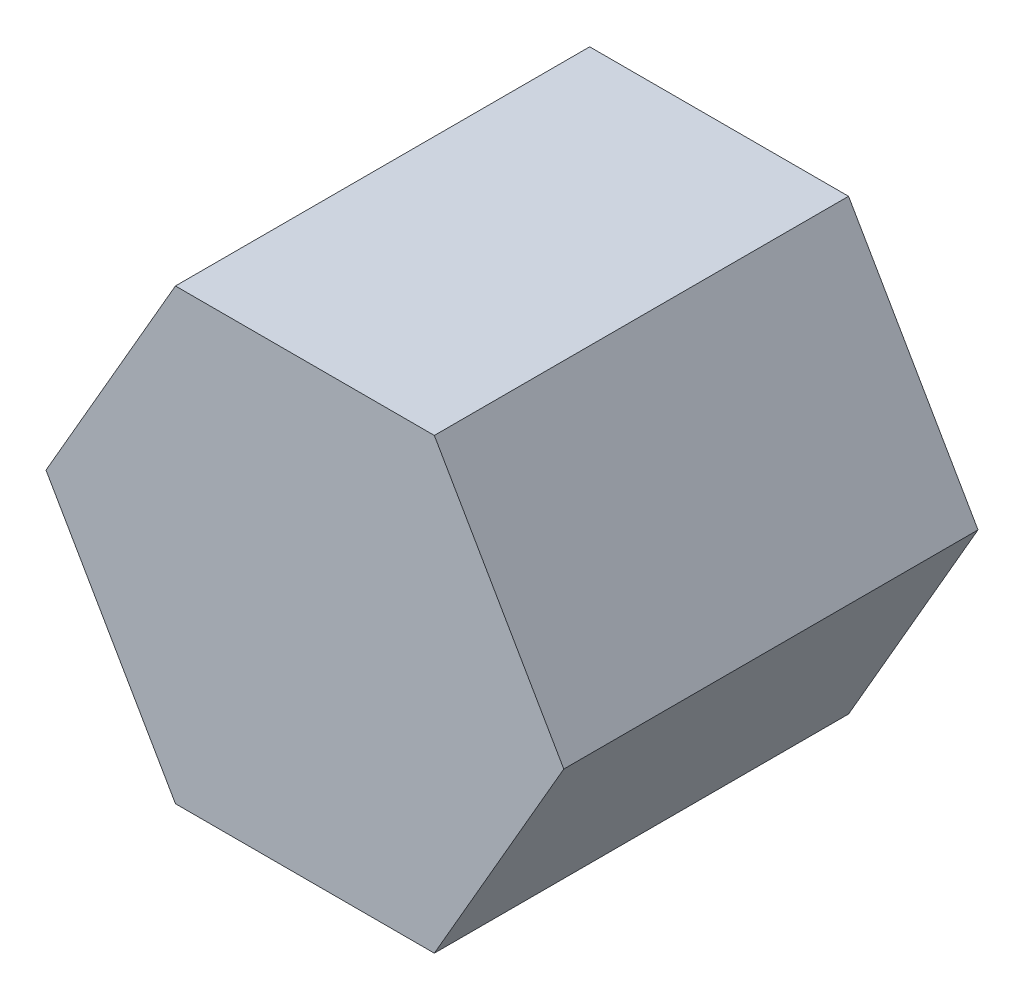
SolidWorks part; units mm, degrees
ref_plane "Front Plane" through (0, 0, 0) normal (0, 0, 1) x (1, 0, 0)
ref_plane "Top Plane" through (0, 0, 0) normal (0, 1, 0) x (1, 0, 0)
ref_plane "Right Plane" through (0, 0, 0) normal (1, 0, 0) x (0, 0, -1)
sketch "Sketch1" plane through (0, 0, 0) normal (0, 0, 1) x (1, 0, 0)
  line L0 (-19.1171, 22.1879) -> (-14.1171, 22.1879)
  line L1 (-14.1171, 22.1879) -> (-11.6171, 17.8578)
  line L2 (-11.6171, 17.8578) -> (-14.1171, 13.5276)
  line L3 (-14.1171, 13.5276) -> (-19.1171, 13.5276)
  line L4 (-19.1171, 13.5276) -> (-21.6171, 17.8578)
  line L5 (-21.6171, 17.8578) -> (-19.1171, 22.1879)
  dimension "D1" = 120
  dimension "D2" = 120
  dimension "D3" = 120
  dimension "D4" = 120
  dimension "D5" = 120
  dimension "D6" = 120
  dimension "D7" = 10
extrude "Boss-Extrude1" add sketch "Sketch1" along normal blind 8
